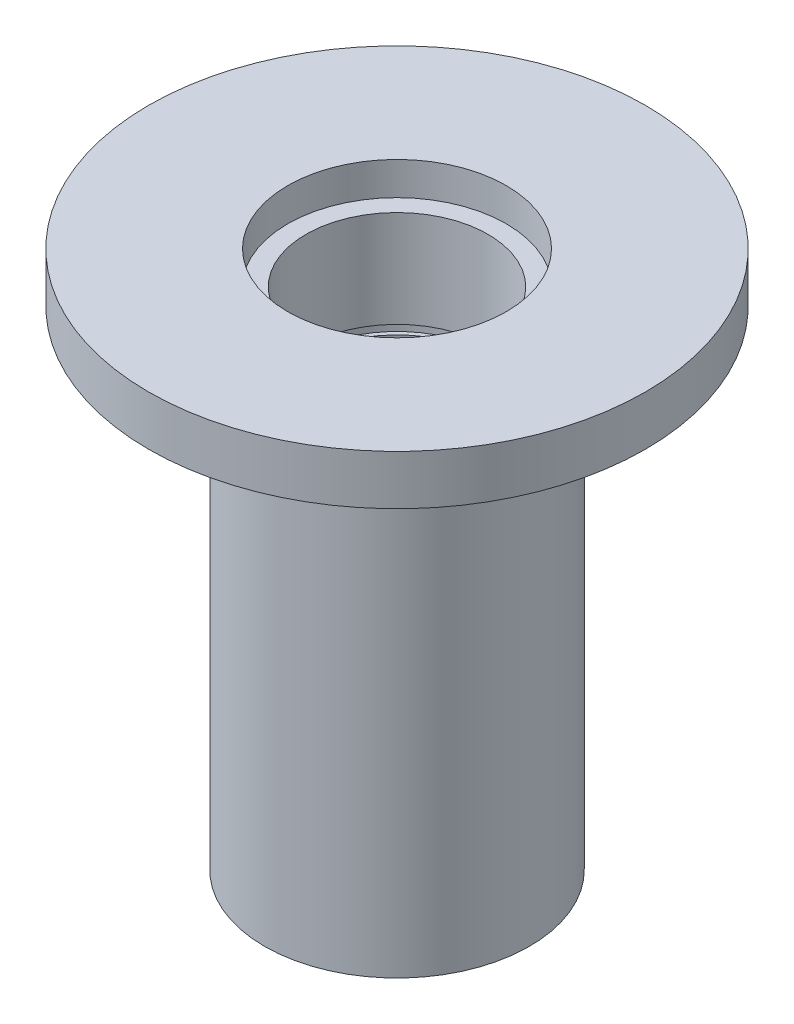
SolidWorks part; units mm, degrees
ref_plane "Front Plane" through (0, 0, 0) normal (0, 0, 1) x (1, 0, 0)
ref_plane "Top Plane" through (0, 0, 0) normal (0, 1, 0) x (1, 0, 0)
ref_plane "Right Plane" through (0, 0, 0) normal (1, 0, 0) x (0, 0, -1)
sketch "Sketch1" plane through (0, 0, 0) normal (0, 0, 1) x (1, 0, 0)
  line L0 (0, 0) -> (0, -122.9972) construction
  line L1 (30, 0) -> (13.2, 0)
  line L2 (13.2, 0) -> (13.2, -4)
  line L3 (13.2, -4) -> (11, -4)
  line L4 (11, -4) -> (11, -15.7)
  line L9 (11, -65) -> (16, -65)
  line L10 (16, -65) -> (16, -6)
  line L11 (16, -6) -> (30, -6)
  line L12 (30, -6) -> (30, 0)
  line L13 (11, -16.8) -> (11, -31.2)
  line L14 (11, -15.7) -> (11.5, -15.7)
  line L16 (11, -16.8) -> (11.5, -16.8)
  line L17 (11.5, -15.7) -> (11.5, -16.8)
  line L18 (11, -31.2) -> (11.5, -31.2)
  line L20 (11, -32.3) -> (11.5, -32.3)
  line L21 (11.5, -31.2) -> (11.5, -32.3)
  line L22 (11, -32.3) -> (11, -65)
  dimension "D1" = 22
  dimension "D2" = 26.4
  dimension "D3" = 4
  dimension "D4" = 15.7
  dimension "D5" = 1.1
  dimension "D6" = 23
  dimension "D7" = 32.3
  dimension "D8" = 65
  dimension "D9" = 6
  dimension "D10" = 32
  dimension "D11" = 60
revolve "Revolve1" add sketch "Sketch1" angle 360 about L0
